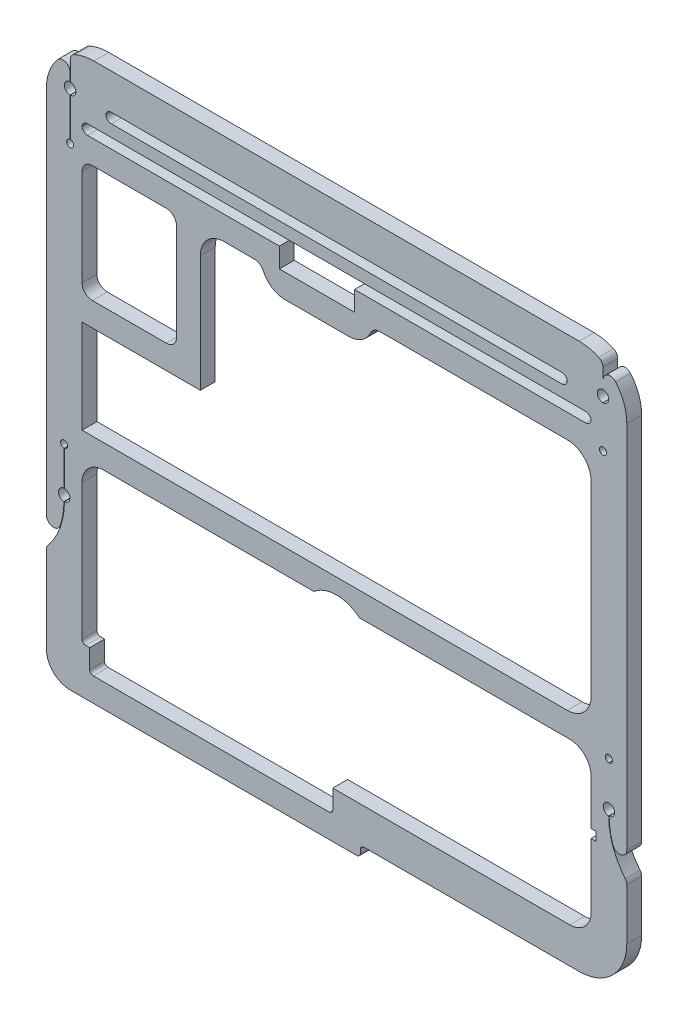
SolidWorks part; units mm, degrees
ref_plane "Front Plane" through (0, 0, 0) normal (0, 0, 1) x (1, 0, 0)
ref_plane "Top Plane" through (0, 0, 0) normal (0, 1, 0) x (1, 0, 0)
ref_plane "Right Plane" through (0, 0, 0) normal (1, 0, 0) x (0, 0, -1)
sketch "Sketch1" plane through (0, 0, 0) normal (0, 0, 1) x (1, 0, 0)
  line L0 (63.9883, 88.3985) -> (63.9883, 84.5885) construction
  line L1 (48.2422, 30.1083) -> (110.2188, 30.1083)
  line L2 (48.2422, 30.1083) -> (48.2422, 88.3985)
  line L3 (48.2422, 88.3985) -> (110.2188, 88.3985)
  line L4 (110.2188, 30.1083) -> (110.2188, 88.3985)
  line L5 (106.4088, 84.5885) -> (52.0522, 84.5885)
  line L6 (106.4088, 84.5885) -> (106.4088, 33.9183)
  line L7 (106.4088, 33.9183) -> (52.0522, 33.9183)
  line L8 (52.0522, 84.5885) -> (52.0522, 33.9183)
  line L9 (63.9883, 86.4935) -> (18.0707, 86.4935) construction
  line L10 (52.0522, 41.2855) -> (48.2422, 41.2855) construction
  line L11 (50.1472, 41.2855) -> (50.1472, 25.8577) construction
  line L12 (13.5248, 33.9183) -> (13.5248, 30.1083) construction
  line L13 (13.5248, 32.0133) -> (21.1598, 32.0133) construction
  line L14 (110.2188, 38.1916) -> (106.4088, 38.1916) construction
  line L15 (108.3138, 38.1916) -> (108.3138, 22.3321) construction
  line L16 (106.4088, 54.6152) -> (106.4088, 79.5085) construction
  line L17 (52.0522, 74.5555) -> (52.0522, 54.6152) construction
  line L22 (79.0876, 86.4935) -> (79.6338, 86.4935) construction
  line L23 (96.5564, 32.0133) -> (96.0102, 32.0133) construction
  dimension "D1" = 3.81
  dimension "D2" = 3.81
extrude "Boss-Extrude1" add sketch "Sketch1" along normal blind 1.5875
sketch "Sketch2" plane through (0, 0, 0) normal (0, 0, -1) x (-1, 0, 0)
  line L0 (-106.4088, 33.9183) -> (-106.4088, 84.5885) construction
  line L1 (-106.4088, 53.6273) -> (-52.0522, 53.6273)
  line L2 (-106.4088, 53.6273) -> (-106.4088, 51.0873)
  line L3 (-106.4088, 51.0873) -> (-52.0522, 51.0873)
  line L4 (-52.0522, 53.6273) -> (-52.0522, 51.0873)
  line L5 (-52.0522, 84.5885) -> (-52.0522, 33.9183) construction
  line L6 (-57.1852, 53.6273) -> (-94.8852, 53.6273) construction
  line L8 (-99.4108, 81.1849) -> (-61.0568, 81.1849) construction
  line L9 (-80.5132, 79.0767) -> (-73.7568, 79.0767) construction
  line L10 (-80.5132, 81.1849) -> (-80.5132, 79.0767) construction
  line L11 (-106.4088, 81.1849) -> (-81.1482, 81.1849)
  line L12 (-106.4088, 81.1849) -> (-106.4088, 78.6449)
  line L13 (-106.4088, 78.6449) -> (-83.0532, 78.6449)
  line L14 (-52.0522, 81.1849) -> (-52.0522, 78.6449)
  line L15 (-106.4088, 83.5217) -> (-52.0522, 83.5217)
  line L16 (-106.4088, 83.5217) -> (-106.4088, 82.2517)
  line L17 (-106.4088, 82.2517) -> (-52.0522, 82.2517)
  line L18 (-52.0522, 83.5217) -> (-52.0522, 82.2517)
  line L19 (-73.7568, 79.0767) -> (-73.7568, 81.1849) construction
  line L20 (-80.5132, 81.1849) -> (-80.5132, 79.0767) construction
  line L21 (-73.7568, 79.0767) -> (-73.7568, 81.1849) construction
  line L22 (-81.1482, 79.0767) -> (-81.1482, 81.1849)
  line L23 (-73.1218, 79.0767) -> (-81.1482, 79.0767)
  line L24 (-73.1218, 79.0767) -> (-73.1218, 81.1849)
  line L25 (-83.0532, 78.6449) -> (-83.0532, 76.5367)
  line L26 (-83.0532, 76.5367) -> (-71.2168, 76.5367)
  line L27 (-71.2168, 76.5367) -> (-71.2168, 78.6449)
  line L28 (-71.2168, 78.6449) -> (-52.0522, 78.6449)
  line L29 (-73.1218, 81.1849) -> (-52.0522, 81.1849)
  line L30 (-81.1482, 42.249) -> (-80.5132, 42.249) construction
  line L31 (-57.9086, 84.5885) -> (-57.9086, 83.5217) construction
  line L32 (-73.7568, 42.1673) -> (-73.1218, 42.1673) construction
  line L33 (-106.4088, 84.5885) -> (-52.0522, 84.5885) construction
  line L35 (-57.9086, 82.2517) -> (-57.9086, 81.1849) construction
  dimension "D1" = 2.54
  dimension "D2" = 1.905
  dimension "D3" = 2.54
  dimension "D4" = 1.905
  dimension "D5" = 1.27
  dimension "D6" = 0.635
extrude "Boss-Extrude2" add sketch "Sketch2" against normal up to surface (1.5875 mm away) up to face at (79.2305, 59.2534, 1.5875)
sketch "Sketch3" plane through (0, 0, 0) normal (0, 0, -1) x (-1, 0, 0)
  line L1 (-60.4352, 63.6273) -> (-52.0522, 63.6273) construction
  line L12 (-64.6852, 63.6273) -> (-13.0532, 63.6273)
  line L13 (-13.0532, 63.6273) -> (-52.0522, 63.6273)
  line L14 (-52.0522, 78.6449) -> (-52.0522, 53.6273) construction
  line L15 (-52.0522, 63.6273) -> (-52.0522, 66.1673)
  line L16 (-52.0522, 66.1673) -> (-62.1452, 66.1673)
  line L17 (-62.1452, 66.1673) -> (-62.1452, 78.6449)
  line L18 (-71.2168, 78.6449) -> (-52.0522, 78.6449) construction
  line L19 (-62.1452, 78.6449) -> (-64.6852, 78.6449)
  line L20 (-64.6852, 78.6449) -> (-64.6852, 63.6273)
  line M27 (-71.2168, 78.6449) -> (-52.0522, 78.6449)
  line M28 (-52.0522, 78.6449) -> (-52.0522, 53.6273)
  dimension "D3" = 2.54
  dimension "D4" = 2.54
extrude "Boss-Extrude3" add sketch "Sketch3" against normal up to surface (1.5875 mm away) contours L20 L12 L13 L16 L17 M27 M28 region at (64.4889, 71.1361, 0) up to face at (79.2305, 84.0551, 1.5875)
sketch "Sketch5" plane through (0, 0, 0) normal (0, 0, -1) x (-1, 0, 0)
  line L1 (-52.8684, 31.5053) -> (-78.8272, 31.5053) construction
  line L2 (-52.8684, 31.5053) -> (-52.8684, 43.964) construction
  line L6 (-52.8684, 43.964) -> (-78.8272, 43.964) construction
  line L7 (-78.8272, 31.5053) -> (-78.8272, 43.964) construction
  line L8 (-52.8684, 31.5053) -> (-78.8272, 31.5053)
  line L9 (-52.8684, 31.5053) -> (-52.8684, 43.964)
  line L10 (-52.8684, 43.964) -> (-78.8272, 43.964)
  line L11 (-78.8272, 31.5053) -> (-78.8272, 43.964)
  circle A1 centre (-79.2305, 48.2171) radius 3.7592 construction
  circle A2 centre (-79.2305, 48.2171) radius 3.7592
extrude "Cut-Extrude1" cut sketch "Sketch5" against normal up to surface (1.5875 mm away) up to face at (57.0987, 72.4061, 1.5875)
fillet "Fillet1" radius 5.08 3 edges at (110.2188, 30.1083, 0.7937) (48.2422, 88.3985, 0.7937) (110.2188, 88.3985, 0.7937)
fillet "Fillet2" radius 2.54 5 edges at (64.6852, 78.6449, 0.7937) (71.2168, 76.5367, 0.7937) (106.4088, 78.6449, 0.7937) (106.4088, 53.6273, 0.7937) (83.0532, 76.5367, 0.7937)
fillet "Fillet3" radius 1.0922 6 edges at (52.0522, 66.1673, 0.7937) (62.1452, 66.1673, 0.7937) (52.0522, 78.6449, 0.7937) (62.1452, 78.6449, 0.7937) (71.2168, 78.6449, 0.7937) (83.0532, 78.6449, 0.7937)
fillet "Fillet4" radius 0.5842 4 edges at (52.0522, 81.1849, 0.7937) (52.0522, 82.2517, 0.7938) (106.4088, 82.2517, 0.7937) (106.4088, 81.1849, 0.7937)
sketch "Sketch6" plane through (0, 0, 0) normal (0, 0, -1) x (-1, 0, 0)
  line L0 (-53.6852, 62.1273) -> (-53.6852, 55.1273) construction
  line L1 (-53.6852, 62.1273) -> (-53.6852, 55.1273)
  line L2 (-55.1852, 63.6273) -> (-53.6852, 62.1273) construction
  line L3 (-55.1852, 63.6273) -> (-53.6852, 62.1273)
  line L4 (-55.1852, 63.6273) -> (-55.1852, 53.6273)
  line L6 (-57.1852, 55.1273) -> (-57.1852, 53.6273)
  line L7 (-57.1852, 53.6273) -> (-55.1852, 53.6273)
  line L8 (-55.1852, 53.6273) -> (-53.6852, 55.1273)
  line L9 (-53.6852, 55.1273) -> (-57.1852, 55.1273)
  line L12 (-55.1852, 53.6273) -> (-53.6852, 55.1273)
  circle A0 centre (-107.6788, 84.5885) radius 0.6096 construction
  circle A1 centre (-50.7822, 84.5885) radius 0.6096 construction
  circle A2 centre (-108.3138, 46.6777) radius 0.6096 construction
  circle A3 centre (-50.1472, 46.6777) radius 0.6096 construction
  circle A4 centre (-107.6788, 84.5885) radius 0.6096
  circle A5 centre (-50.7822, 84.5885) radius 0.6096
  circle A6 centre (-108.3138, 46.6777) radius 0.6096
  circle A7 centre (-50.1472, 46.6777) radius 0.6096
  dimension "D1" = 0
extrude "Cut-Extrude2" cut sketch "Sketch6" against normal up to surface (1.5875 mm away) up to face at (57.0987, 72.4061, 1.5875)
sketch "Sketch9" plane through (0, 0, 1.5875) normal (0, 0, 1) x (1, 0, 0)
  line L4 (106.945, 43.964) -> (81.3672, 43.964)
  line L5 (81.3672, 43.964) -> (81.3672, 43.0496)
  line L6 (81.3672, 43.0496) -> (106.945, 43.0496)
  line L7 (106.945, 43.0496) -> (106.945, 43.964)
  line L8 (106.945, 43.964) -> (81.3672, 43.964)
  line L9 (81.3672, 43.964) -> (81.3672, 43.0496)
  line L10 (81.3672, 43.0496) -> (106.945, 43.0496)
  line L11 (106.945, 43.0496) -> (106.945, 43.964)
  dimension "D1" = 0
extrude "Cut-Extrude3" cut sketch "Sketch9" against normal up to surface (1.5875 mm away) up to face at (49.5376, 46.6777, 0)
sketch "Sketch11" plane through (0, 0, 1.5875) normal (0, 0, 1) x (1, 0, 0)
  line L0 (52.8684, 31.5053) -> (78.8272, 31.5053) construction
  line L1 (48.2422, 30.1083) -> (81.7705, 30.1083)
  line L2 (48.2422, 30.1083) -> (48.2422, 28.9653)
  line L3 (48.2422, 28.9653) -> (81.7705, 28.9653)
  line L4 (81.7705, 30.1083) -> (81.7705, 28.9653)
  line L5 (79.2305, 51.9763) -> (79.2305, -22.2214) construction
  circle A0 centre (79.2305, 48.2171) radius 3.7592 construction
  dimension "D1" = 2.54
  dimension "D2" = 2.54
extrude "Boss-Extrude6" add sketch "Sketch11" against normal up to surface (1.5875 mm away) up to face at (83.2487, 41.2821, 0)
fillet "Fillet7" radius 2.54 1 edges at (48.2422, 28.9653, 0.7937)
fillet "Fillet8" radius 0.381 2 edges at (81.7705, 28.9653, 0.7937) (81.7705, 30.1083, 0.7937)
sketch "Sketch12" plane through (0, 0, 1.5875) normal (0, 0, 1) x (1, 0, 0)
  line L0 (52.0522, 84.5885) -> (52.0522, 83.5217) construction
  line L1 (52.0522, 84.5885) -> (54.5922, 84.5885)
  line L2 (52.0522, 84.5885) -> (52.0522, 83.5217)
  line L3 (52.0522, 83.5217) -> (54.5922, 83.5217)
  line L4 (54.5922, 84.5885) -> (54.5922, 83.5217)
  line L5 (106.4088, 84.5885) -> (52.0522, 84.5885) construction
  line L6 (106.4088, 83.5217) -> (52.0522, 83.5217) construction
  line L8 (106.4088, 84.5885) -> (103.8688, 84.5885)
  line L9 (106.4088, 84.5885) -> (106.4088, 83.5217)
  line L10 (106.4088, 83.5217) -> (103.8688, 83.5217)
  line L11 (103.8688, 84.5885) -> (103.8688, 83.5217)
  dimension "D1" = 2.54
extrude "Boss-Extrude7" add sketch "Sketch12" against normal up to surface (1.5875 mm away) up to face at (83.2487, 41.2821, 0)
fillet "Fillet11" radius 0.5842 4 edges at (103.8688, 83.5217, 0.7937) (103.8688, 84.5885, 0.7937) (54.5922, 83.5217, 0.7937) (54.5922, 84.5885, 0.7937)
sketch "Sketch13" plane through (0, 0, 1.5875) normal (0, 0, 1) x (1, 0, 0)
  line L0 (50.7695, 86.0858) -> (50.7695, 85.198) construction
  line L1 (50.7949, 85.198) -> (50.7949, 87.2592) construction
  line L2 (50.7695, 83.9791) -> (50.7695, 79.8893) construction
  line L3 (50.7949, 79.8893) -> (50.7949, 83.9791) construction
  line L4 (107.6661, 85.198) -> (107.6661, 87.2592) construction
  line L5 (107.6915, 83.9791) -> (107.6915, 79.8893) construction
  line L6 (107.6661, 79.8893) -> (107.6661, 83.9791) construction
  line L7 (108.3265, 50.9963) -> (108.3265, 47.2872) construction
  line L8 (108.3011, 50.9963) -> (108.3011, 47.2872) construction
  line L9 (50.1345, 50.9963) -> (50.1345, 47.2872) construction
  line L10 (50.1599, 50.9963) -> (50.1599, 47.2872) construction
  line L11 (50.7695, 86.0858) -> (50.7695, 85.198)
  line L12 (50.7949, 85.198) -> (50.7949, 87.2592)
  line L13 (50.7695, 83.9791) -> (50.7695, 79.8893)
  line L14 (50.7949, 79.8893) -> (50.7949, 83.9791)
  line L15 (107.6661, 85.198) -> (107.6661, 87.2592)
  line L16 (107.6915, 83.9791) -> (107.6915, 79.8893)
  line L17 (107.6661, 79.8893) -> (107.6661, 83.9791)
  line L18 (108.3265, 50.9963) -> (108.3265, 47.2872)
  line L19 (108.3011, 50.9963) -> (108.3011, 47.2872)
  line L20 (50.1345, 50.9963) -> (50.1345, 47.2872)
  line L21 (50.1599, 50.9963) -> (50.1599, 47.2872)
  line L22 (48.2422, 83.3185) -> (48.2422, 31.5053) construction
  line L23 (110.2188, 35.1883) -> (110.2188, 83.3185) construction
  line L24 (48.2422, 43.8754) -> (48.2422, 40.6699)
  line L25 (110.2188, 40.6699) -> (110.2188, 43.8754)
  line L26 (107.6915, 83.9791) -> (107.6915, 79.8893)
  line L27 (107.6915, 86.0858) -> (107.6915, 85.198) construction
  line L28 (107.6915, 86.0858) -> (107.6915, 85.198)
  arc A0 (107.6661, 83.9791) -> (107.6915, 83.9791) centre (107.6788, 84.5885) ccw
  arc A1 (50.7695, 86.0858) -> (49.4225, 86.5742) centre (50.0075, 86.0858) ccw construction
  arc A2 (51.2454, 87.9546) -> (50.7949, 87.2592) centre (51.5569, 87.2592) ccw construction
  arc A3 (50.7695, 79.8893) -> (50.7949, 79.8893) centre (50.7822, 79.5085) ccw construction
  arc A4 (107.6661, 87.2592) -> (107.2156, 87.9546) centre (106.9041, 87.2592) ccw construction
  arc A5 (109.0384, 86.5742) -> (107.6915, 86.0858) centre (108.4535, 86.0858) ccw construction
  arc A6 (107.6661, 79.8893) -> (107.6915, 79.8893) centre (107.6788, 79.5085) ccw construction
  arc A7 (108.3265, 50.9963) -> (108.3011, 50.9963) centre (108.3138, 51.3771) ccw construction
  arc A8 (108.3392, 46.0687) -> (108.7338, 43.6346) centre (116.0396, 46.0681) ccw construction
  arc A9 (108.7338, 43.6346) -> (110.2188, 43.8754) centre (109.4568, 43.8754) ccw construction
  arc A10 (108.2884, 46.0687) -> (110.046, 41.153) centre (116.0396, 46.0681) ccw construction
  arc A11 (110.2188, 40.6699) -> (110.046, 41.153) centre (109.4568, 40.6699) ccw construction
  arc A12 (48.2422, 43.8754) -> (49.7271, 43.6346) centre (49.0042, 43.8754) ccw construction
  arc A13 (50.1599, 50.9963) -> (50.1345, 50.9963) centre (50.1472, 51.3771) ccw construction
  arc A14 (48.415, 41.153) -> (50.1726, 46.0687) centre (42.4214, 46.0681) ccw construction
  arc A15 (49.7271, 43.6346) -> (50.1218, 46.0687) centre (42.4214, 46.0681) ccw construction
  arc A16 (48.415, 41.153) -> (48.2422, 40.6699) centre (49.0042, 40.6699) ccw construction
  arc A17 (50.7695, 83.9791) -> (50.7949, 83.9791) centre (50.7822, 84.5885) ccw
  arc A18 (50.7695, 86.0858) -> (49.4225, 86.5742) centre (50.0075, 86.0858) ccw
  arc A19 (51.2454, 87.9546) -> (50.7949, 87.2592) centre (51.5569, 87.2592) ccw
  arc A20 (50.7695, 79.8893) -> (50.7949, 79.8893) centre (50.7822, 79.5085) ccw
  arc A21 (107.6661, 87.2592) -> (107.2156, 87.9546) centre (106.9041, 87.2592) ccw
  arc A22 (109.0384, 86.5742) -> (107.6915, 86.0858) centre (108.4535, 86.0858) ccw
  arc A23 (107.6661, 79.8893) -> (107.6915, 79.8893) centre (107.6788, 79.5085) ccw
  arc A24 (108.3265, 50.9963) -> (108.3011, 50.9963) centre (108.3138, 51.3771) ccw
  arc A25 (108.3392, 46.0687) -> (108.7338, 43.6346) centre (116.0396, 46.0681) ccw
  arc A26 (108.7338, 43.6346) -> (110.2188, 43.8754) centre (109.4568, 43.8754) ccw
  arc A27 (108.2884, 46.0687) -> (110.046, 41.153) centre (116.0396, 46.0681) ccw
  arc A28 (110.2188, 40.6699) -> (110.046, 41.153) centre (109.4568, 40.6699) ccw
  arc A29 (48.2422, 43.8754) -> (49.7271, 43.6346) centre (49.0042, 43.8754) ccw
  arc A30 (50.1599, 50.9963) -> (50.1345, 50.9963) centre (50.1472, 51.3771) ccw
  arc A31 (48.415, 41.153) -> (50.1726, 46.0687) centre (42.4214, 46.0681) ccw
  arc A32 (49.7271, 43.6346) -> (50.1218, 46.0687) centre (42.4214, 46.0681) ccw
  arc A33 (48.415, 41.153) -> (48.2422, 40.6699) centre (49.0042, 40.6699) ccw
  circle A34 centre (50.7822, 84.5885) radius 0.6096 construction
  circle A35 centre (107.6788, 84.5885) radius 0.6096 construction
  circle A36 centre (108.3138, 46.6777) radius 0.6096 construction
  circle A37 centre (50.1472, 46.6777) radius 0.6096 construction
  arc A38 (53.3222, 88.3985) -> (48.2422, 83.3185) centre (53.3222, 83.3185) ccw construction
  arc A39 (110.2188, 83.3185) -> (105.1388, 88.3985) centre (105.1388, 83.3185) ccw construction
  arc A40 (50.7949, 85.198) -> (50.7695, 85.198) centre (50.7822, 84.5885) ccw
  arc A41 (107.6661, 83.9791) -> (107.6915, 83.9791) centre (107.6788, 84.5885) ccw
  arc A42 (108.3265, 47.2872) -> (108.3011, 47.2872) centre (108.3138, 46.6777) ccw
  arc A43 (50.1218, 46.0687) -> (50.1726, 46.0687) centre (50.1472, 46.6777) ccw
  arc A44 (51.2454, 87.9546) -> (49.4225, 86.5742) centre (53.3222, 83.3185) ccw
  arc A45 (109.0384, 86.5742) -> (107.2156, 87.9546) centre (105.1388, 83.3185) ccw
  arc A46 (50.1599, 47.2872) -> (50.1345, 47.2872) centre (50.1472, 46.6777) ccw
  arc A47 (108.2884, 46.0687) -> (108.3392, 46.0687) centre (108.3138, 46.6777) ccw
  arc A48 (107.6915, 85.198) -> (107.6661, 85.198) centre (107.6788, 84.5885) ccw
extrude "Cut-Extrude4" cut sketch "Sketch13" against normal through all contours A48 L28 A22 A45 A21 L15 | L17 A23 L16 A0 | A47 A27 A28 L25 A26 A25 | A42 L18 A24 L19 | A43 A32 A29 L24 A33 A31 | A46 L21 A30 L20 | A19 A44 A18 L11 A40 L12 | L13 A20 L14 A17 region at (50.4642, 87.0334, 1.5875) region at (50.7822, 79.9586, 1.5875) region at (107.9968, 87.0334, 1.5875) region at (107.6788, 79.9586, 1.5875) region at (108.3138, 50.9944, 1.5875) region at (50.1472, 50.9944, 1.5875) region at (48.8136, 42.5993, 1.5875) region at (109.6474, 42.5993, 1.5875)
fillet "Fillet12" radius 2.286 3 edges at (106.4088, 33.9183, 0.7937) (106.4088, 51.0873, 0.7937) (52.0522, 51.0873, 0.7938)
fillet "Fillet13" radius 0.381 3 edges at (52.0522, 33.9183, 0.7937) (52.8684, 31.5053, 0.7937) (78.8272, 31.5053, 0.7937)
